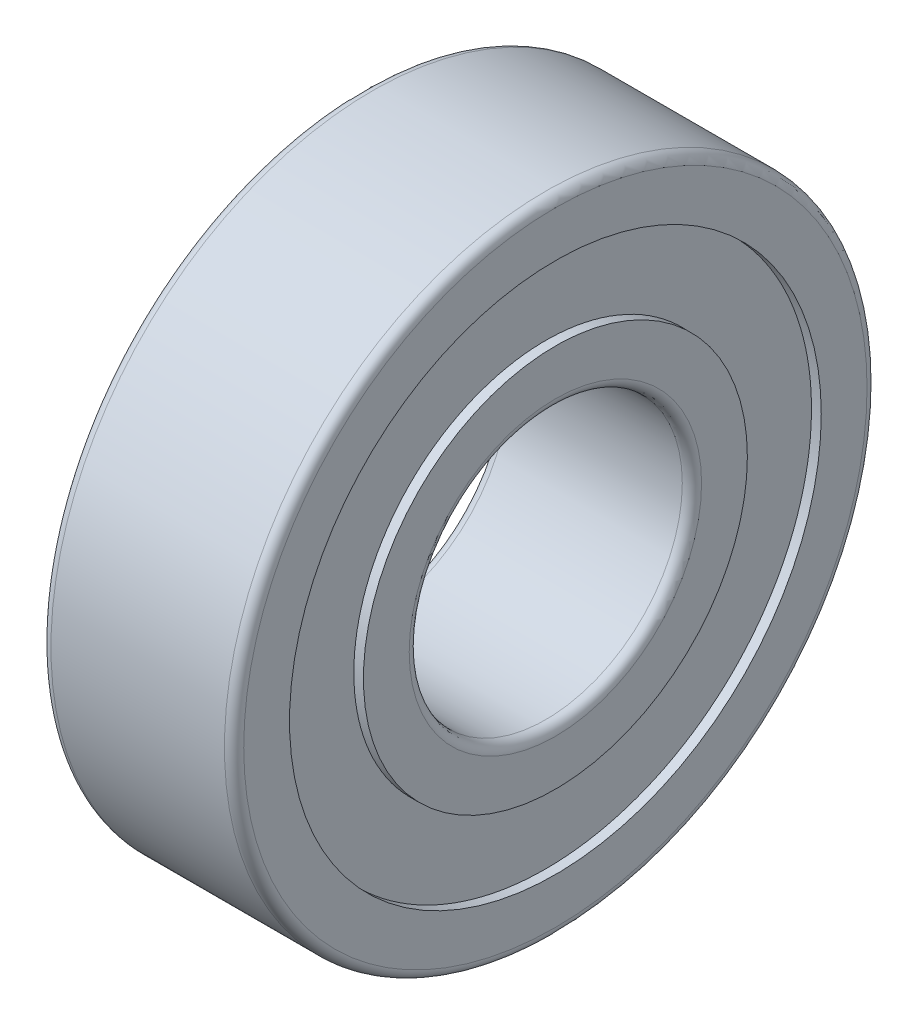
SolidWorks part; units mm, degrees
note: '?' marks a value the reader was unsure of.
ref_plane "Plane1" through (0, 0, 0) normal (0, 0, 1) x (1, 0, 0)
ref_plane "Plane2" through (0, 0, 0) normal (0, 1, 0) x (1, 0, 0)
ref_plane "Plane3" through (0, 0, 0) normal (1, 0, 0) x (0, 0, -1)
ref_axis "Axis1" through (-50, 0, 0) along (1, 0, 0)?
sketch "BalDetSke" plane through (0, 0, 0) normal (0, 0, 1) x (1, 0, 0)
  line L0 (-3.45, 14.25) -> (3.45, 14.25)
  line L1 (-1.905, 14.25) -> (1.905, 14.25) construction
  line L2 (0, 0) -> (0, 25) construction
  arc A0 (3.45, 14.25) -> (-3.45, 14.25) centre (0, 14.25) cw
  dimension "Ball_diameter" = 6.9
  dimension "BallCLRad" = 14.25
revolve "BallDetailed" add sketch "BalDetSke" angle 360 about L1
sketch "InnRacSke" plane through (0, 0, 0) normal (0, 0, 1) x (1, 0, 0)
  line L0 (-2.5378, 11.95) -> (-6, 11.95)
  line L1 (-6, 11.95) -> (-6, 9.1)
  line L2 (-5.4, 8.5) -> (5.4, 8.5)
  line L3 (6, 9.1) -> (6, 11.95)
  line L4 (6, 11.95) -> (2.5378, 11.95)
  line L5 (-20.6375, 0) -> (20.6375, 0) construction
  line L6 (0, 0) -> (0, 30) construction
  arc A0 (-6, 9.1) -> (-5.4, 8.5) centre (-5.4, 9.1) ccw
  arc A1 (5.4, 8.5) -> (6, 9.1) centre (5.4, 9.1) ccw
  arc A2 (2.5378, 11.95) -> (-2.5378, 11.95) centre (0, 14.25) cw
  dimension "Fillet_radius" = 0.6
  dimension "Ball_diameter" = 6.85
  dimension "ID" = 17
  dimension "OD" = 23.9
  dimension "Width" = 12
  dimension "BallCLRad" = 14.25
revolve "InnerRace" add sketch "InnRacSke" angle 360 about L5
sketch "OutRacSke" plane through (0, 0, 0) normal (0, 0, 1) x (1, 0, 0)
  line L0 (-2.5378, 16.55) -> (-6, 16.55)
  line L1 (-6, 16.55) -> (-6, 19.4)
  line L2 (-5.4, 20) -> (5.4, 20)
  line L3 (6, 19.4) -> (6, 16.55)
  line L4 (6, 16.55) -> (2.5378, 16.55)
  line L5 (-20.6375, 0) -> (20.6375, 0) construction
  line L6 (0, 0) -> (0, 30) construction
  arc A0 (-6, 19.4) -> (-5.4, 20) centre (-5.4, 19.4) cw
  arc A1 (5.4, 20) -> (6, 19.4) centre (5.4, 19.4) cw
  arc A2 (2.5378, 16.55) -> (-2.5378, 16.55) centre (0, 14.25) ccw
  dimension "Fillet_radius" = 0.6
  dimension "Ball_diameter" = 6.85
  dimension "OD" = 40
  dimension "ID" = 33.1
  dimension "Width" = 12
  dimension "BallCLRad" = 14.25
revolve "OuterRace" add sketch "OutRacSke" angle 360 about L5
pattern_circular "Répétition circulaire1" count 10 over 360 about axis through (0, 0, 0) along (1, 0, 0) of bodies 102
sketch "Esquisse1" plane through (0, 0, 0) normal (0, 0, 1) x (1, 0, 0)
  line L4 (5.4, 16.55) -> (5.4, 11.95)
  line L5 (6, 16.55) -> (2.5378, 16.55) construction
  line L6 (5.4, 20) -> (5.4, -20) construction
  line L7 (6, 11.95) -> (2.5378, 11.95) construction
revolve "Révol.-Mince3" add sketch "Esquisse1" angle 360 about L5
sketch "Esquisse2" plane through (0, 0, 0) normal (0, 0, 1) x (1, 0, 0)
  line L0 (-5.4, 16.55) -> (-5.4, 11.95)
  line L1 (-2.5378, 16.55) -> (-6, 16.55) construction
  line L2 (-5.4, 20) -> (-5.4, -20) construction
  line L3 (-2.5378, 11.95) -> (-6, 11.95) construction
revolve "Révol.-Mince5" add sketch "Esquisse2" angle 360 about L5 wall 0.6
